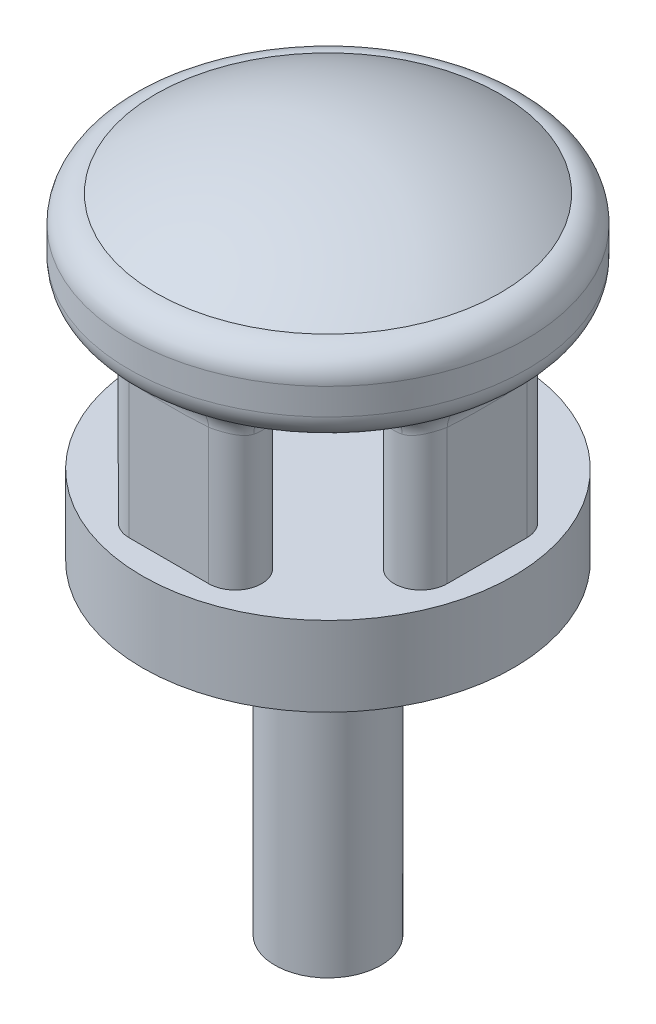
SolidWorks part; units mm, degrees
ref_plane "Front Plane" through (0, 0, 0) normal (0, 0, 1) x (1, 0, 0)
ref_plane "Top Plane" through (0, 0, 0) normal (0, 1, 0) x (1, 0, 0)
ref_plane "Right Plane" through (0, 0, 0) normal (1, 0, 0) x (0, 0, -1)
sketch "Sketch1" plane through (0, 0, 0) normal (0, 1, 0) x (1, 0, 0)
  circle A0 centre (0, 0) radius 9.525
  dimension "D1" = 19.05
extrude "button top" add sketch "Sketch1" along normal blind 3.81
sketch "Sketch2" plane through (0, 0, 0) normal (0, -1, 0) x (1, 0, 0)
  line L9 (-1.905, 6.35) -> (1.905, 6.35) construction
  line L10 (-1.905, 7.62) -> (1.905, 7.62)
  line L11 (-1.905, 5.08) -> (1.905, 5.08)
  arc A6 (-1.905, 7.62) -> (-1.905, 5.08) centre (-1.905, 6.35) ccw
  arc A7 (1.905, 5.08) -> (1.905, 7.62) centre (1.905, 6.35) ccw
  point P22 (0, 6.35)
  dimension "D2" = 1.27
  dimension "D1" = 6.35
  dimension "D8" = 3.81
extrude "connecting leg" add sketch "Sketch2" along normal blind 7.62
ref_axis "central axis" through (0, 3.81, 0) along (0, -1, 0)
pattern_circular "moar legs" count 4 over 360 about axis through (0, 3.81, 0) along (0, -1, 0) of "connecting leg"
ref_plane "base plane" through (0, -7.62, 0) normal (0, -1, 0) x (-1, 0, 0)
sketch "Sketch3" plane through (0, -7.62, 0) normal (0, -1, 0) x (-1, 0, 0)
  circle A0 centre (0, 0) radius 8.89
extrude "base" add sketch "Sketch3" along normal blind 3.81 separate body
fillet "round top" radius 1.27 2 edges at (0, 3.81, 9.525) (0, 0, 9.525)
fillet "round bars" radius 1.27 16 edges at (0, 0, 5.08) (-3.175, 0, 6.35) (0, 0, 7.62) (3.175, 0, 6.35) (5.08, 0, 0) (6.35, 0, 3.175) (7.62, 0, 0) (6.35, 0, -3.175) (3.175, 0, -6.35) (0, 0, -7.62) (-3.175, 0, -6.35) (0, 0, -5.08) (-5.08, 0, 0) (-6.35, 0, -3.175) (-7.62, 0, 0) (-6.35, 0, 3.175)
dome "button ness" faces to dome 1 distance 2.54 reverse direction no elliptical dome no face at (0, 3.81, 8.255) parameters "D1"=2.54
ref_point "center of face"
sketch "Sketch6" plane through (0, -11.43, 0) normal (0, -1, 0) x (1, 0, 0)
  circle A0 centre (0, 0) radius 2.54
extrude "flag" add sketch "Sketch6" along normal blind 15.5169
fillet "flag fillet" radius 2.54 1 edges at (0, -11.43, -2.54)
